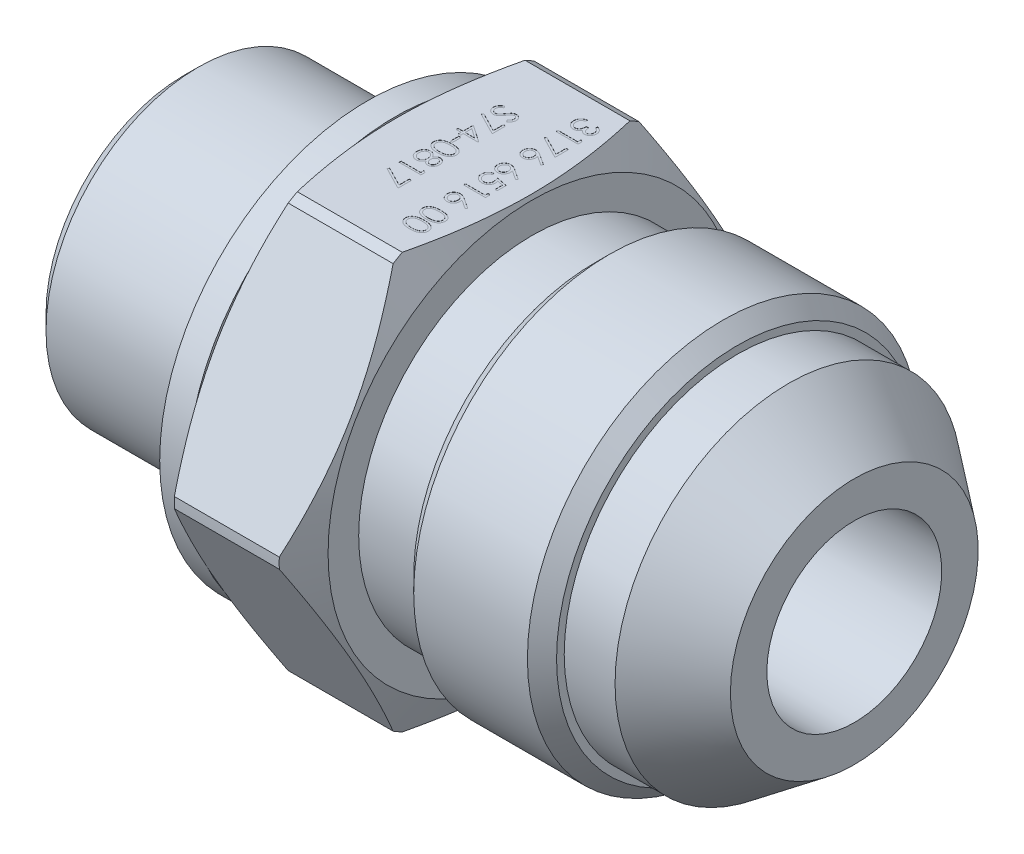
SolidWorks part; units mm, degrees
material "4140 H/T"
ref_plane "Front Plane" through (0, 0, 0) normal (0, 0, 1) x (1, 0, 0)
ref_plane "Top Plane" through (0, 0, 0) normal (0, 1, 0) x (1, 0, 0)
ref_plane "Right Plane" through (0, 0, 0) normal (1, 0, 0) x (0, 0, -1)
sketch "Sketch1" plane through (0, 0, 0) normal (0, 0, 1) x (1, 0, 0)
  line L0 (0, 0) -> (53.9967, 0) construction
  line L1 (0, 7.9) -> (0, 10.45)
  line L2 (11.55, 10.45) -> (12.5, 9.5)
  line L3 (0, 10.45) -> (11.55, 10.45)
  line L4 (14.5, 9.5) -> (14.5, 14)
  line L5 (15.6, 16.25) -> (22.8, 16.25)
  line L6 (23.9, 14) -> (23.9, 11.9)
  line L7 (23.9, 11.9) -> (28.2, 11.9)
  line L8 (28.2, 11.9) -> (28.2, 13.425)
  line L9 (28.2, 13.425) -> (38, 13.425)
  line L10 (38, 13.425) -> (38, 11.9)
  line L11 (38, 11.9) -> (41.488, 11.9)
  line L12 (41.488, 11.9) -> (46, 8.5)
  line L13 (46, 8.5) -> (46, 6)
  line L14 (0, 7.9) -> (3.2909, 6)
  line L18 (46, 6) -> (3.2909, 6)
  line L19 (12.5, 9.5) -> (14.5, 9.5)
  line L20 (15.6, 16.25) -> (14.5, 14)
  line L21 (22.8, 16.25) -> (23.9, 14)
  dimension "D1" = 17
  dimension "D3" = 23.8
  dimension "D4" = 37
  dimension "D5" = 8
  dimension "D6" = 26.85
  dimension "D7" = 17.8
  dimension "D8" = 14.5
  dimension "D9" = 46
  dimension "D10" = 4.3
  dimension "D11" = 20.9
  dimension "D12" = 45
  dimension "D13" = 32.5
  dimension "D14" = 28
  dimension "D15" = 1.1
  dimension "D16" = 1.1
  dimension "D17" = 19
  dimension "D18" = 15.8
  dimension "D19" = 30
  dimension "D21" = 12
  dimension "D22" = 2
revolve "Revolve1" add sketch "Sketch1" angle 360 about L0
cosmetic thread "Cosmetic Thread1" parameters "D2"=19.5
cosmetic thread "Cosmetic Thread2" parameters "D2"=24.5
sketch "Sketch2" plane through (23.9, 0, 0) normal (1, 0, 0) x (0, 0, -1)
  line L1 (8.2272, 14.25) -> (-8.2272, 14.25)
  line L2 (-8.2272, 14.25) -> (-16.4545, 0)
  line L3 (-16.4545, 0) -> (-8.2272, -14.25)
  line L4 (-8.2272, -14.25) -> (8.2272, -14.25)
  line L5 (8.2272, -14.25) -> (16.4545, 0)
  line L6 (16.4545, 0) -> (8.2272, 14.25)
  circle A0 centre (0, 0) radius 14.25 construction
  dimension "D1" = 28.5
extrude "Extrude1" cut sketch "Sketch2" against normal up to surface (9.4 mm away) flip side to cut up to face at (14.5, 0, 9.5)
sketch "Sketch3" plane through (14.5, 0, 0) normal (-1, 0, 0) x (0, 0, 1)
  circle A0 centre (0, 0) radius 14.25
  circle A1 centre (0, 0) radius 11.5
  dimension "D1" = 28.5
  dimension "D2" = 23
extrude "Extrude2" add sketch "Sketch3" along normal blind 1.9
chamfer "Chamfer1" distance 1 angle 45 1 edges at (0, 0, 10.45)
chamfer "Chamfer2" distance 1 angle 45 2 edges at (38, 0, 13.425) (28.2, 0, 13.425)
sketch "Sketch4" plane through (0, 14.25, 0) normal (0, 1, 0) x (1, 0, 0)
  line L0 (20.9, 8.5035) -> (20.9, -8.2954) construction
  line L2 (23.9, -11.9) -> (23.9, 11.9) construction
  text T0 "3176 6516 00\r\nS74-0817" font "Century Gothic" height 1.5
  dimension "D1" = 3
extrude "Cut-Extrude1" cut sketch "Sketch4" against normal blind 0.01
sketch "Sketch5" plane through (0, 0, 0) normal (0, 0, 1) x (1, 0, 0)
  line L0 (0, 0) -> (21.6842, 0) construction
  line L1 (0, 7.9) -> (0, -7.9) construction
  line L2 (14.5, -14.25) -> (14.5, 14.25) construction
  circle A0 centre (13.25, 10.5) radius 1.25
  dimension "D1" = 21
  dimension "D2" = 2.5
revolve "Revolve2" add sketch "Sketch5" angle 360 about L0
